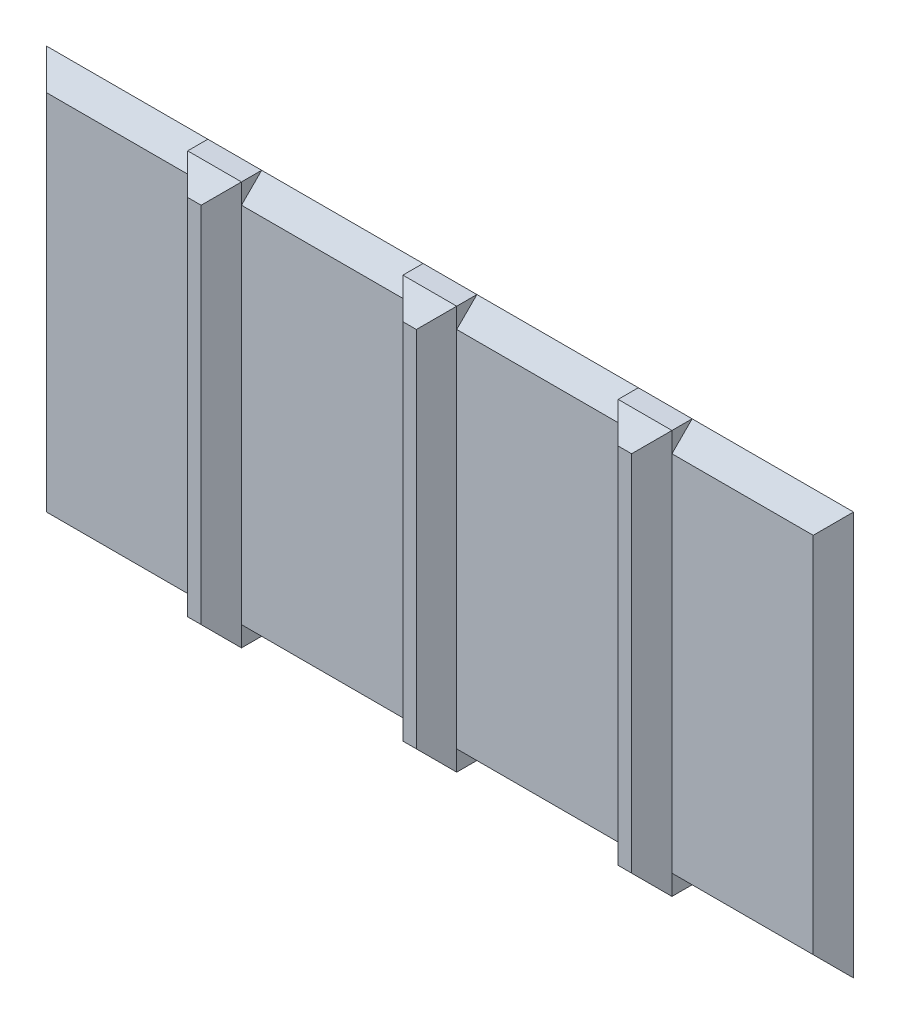
SolidWorks part; units mm, degrees
ref_plane "Front Plane" through (0, 0, 0) normal (0, 0, 1) x (1, 0, 0)
ref_plane "Top Plane" through (0, 0, 0) normal (0, 1, 0) x (1, 0, 0)
ref_plane "Right Plane" through (0, 0, 0) normal (1, 0, 0) x (0, 0, -1)
sketch "Sketch1" plane through (0, 0, 0) normal (0, 0, 1) x (1, 0, 0)
  line L1 (0, 0) -> (10.16, 0)
  line L2 (0, 0) -> (0, 5.08)
  line L3 (0, 5.08) -> (10.16, 5.08)
  line L4 (10.16, 0) -> (10.16, 5.08)
  dimension "D1" = 5.08
  dimension "D2" = 10.16
extrude "Boss-Extrude1" add sketch "Sketch1" along normal blind 0.508
sketch "Sketch2" plane through (0, 0, 0.508) normal (0, 0, 1) x (1, 0, 0)
  line L0 (2.032, 5.08) -> (2.032, 0)
  line L1 (10.16, 5.08) -> (0, 5.08) construction
  line L2 (0, 0) -> (10.16, 0) construction
  line L3 (2.7093, 5.08) -> (2.7093, 0)
  line L4 (4.7413, 5.08) -> (4.7413, 0)
  line L5 (5.4187, 5.08) -> (5.4187, 0)
  line L6 (7.4507, 5.08) -> (7.4507, 0)
  line L7 (8.128, 5.08) -> (8.128, 0)
  line L8 (2.032, 5.08) -> (2.7093, 5.08)
  line L9 (2.032, 0) -> (2.7093, 0)
  line L10 (4.7413, 5.08) -> (5.4187, 5.08)
  line L11 (7.4507, 5.08) -> (8.128, 5.08)
  line L12 (7.4507, 0) -> (8.128, 0)
  line L13 (4.7413, 0) -> (5.4187, 0)
  line L14 (0, 5.08) -> (0, 0) construction
  point P18 (0, 0)
  dimension "D1" = 0.6773
  dimension "D2" = 0.6773
  dimension "D3" = 0.6773
  dimension "D4" = 2.032
  dimension "D5" = 2.032
  dimension "D6" = 2.032
extrude "Boss-Extrude2" add sketch "Sketch2" along normal blind 0.254 contours L0 L9 L3 L8 | L13 L5 L10 L4 | L12 L7 L11 L6
chamfer "Chamfer3" distance 0.254 angle 45 12 edges at (5.08, 5.08, 0) (10.16, 2.54, 0) (5.08, 0, 0) (1.016, 0, 0.508) (3.7253, 0, 0.508) (6.4347, 0, 0.508) (9.144, 0, 0.508) (10.16, 2.54, 0.508) (9.144, 5.08, 0.508) (6.4347, 5.08, 0.508) (3.7253, 5.08, 0.508) (1.016, 5.08, 0.508)
chamfer "Chamfer4" distance 0.254 angle 45 2 edges at (0, 2.54, 0) (0, 2.54, 0.508)
chamfer "Chamfer5" distance 0.254 angle 45 12 edges at (8.128, 2.54, 0.762) (7.7894, 5.08, 0.762) (7.4507, 2.54, 0.762) (7.7894, 0, 0.762) (5.08, 0, 0.762) (5.4187, 2.54, 0.762) (4.7413, 2.54, 0.762) (5.08, 5.08, 0.762) (2.3707, 5.08, 0.762) (2.032, 2.54, 0.762) (2.7093, 2.54, 0.762) (2.3707, 0, 0.762)
